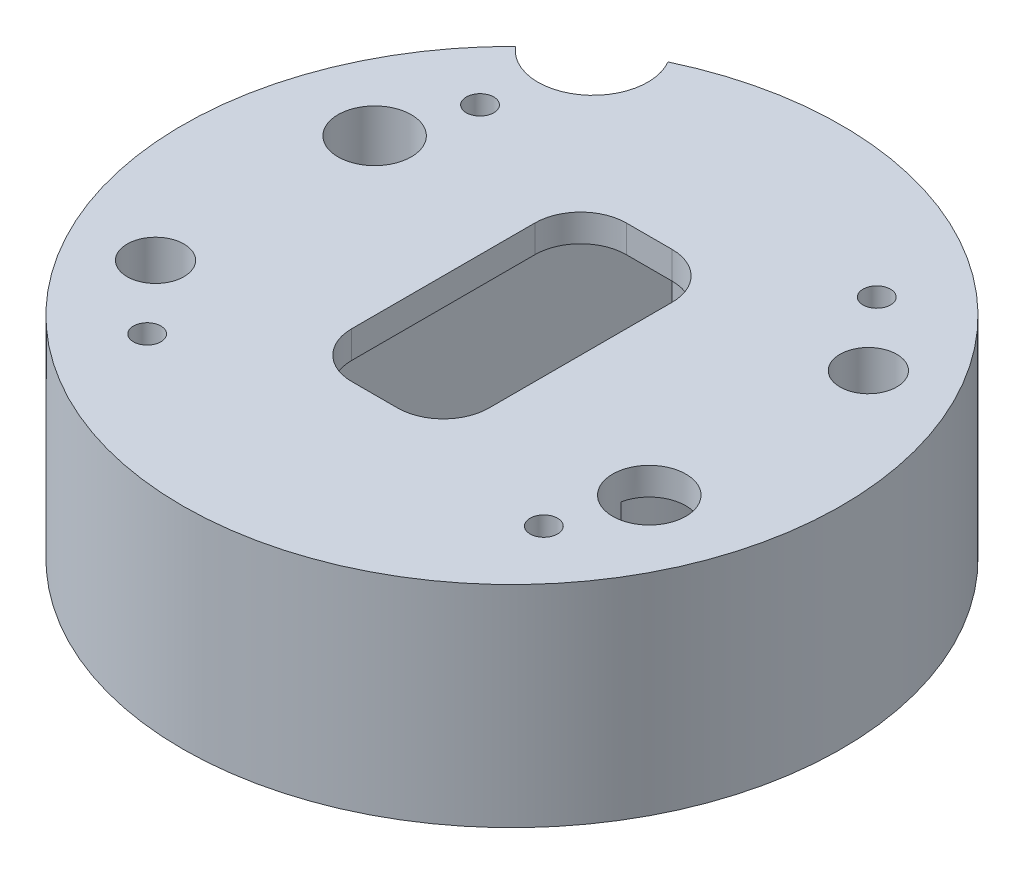
SolidWorks part; units mm, degrees
ref_plane "Front Plane" through (0, 0, 0) normal (0, 0, 1) x (1, 0, 0)
ref_plane "Top Plane" through (0, 0, 0) normal (0, 1, 0) x (1, 0, 0)
ref_plane "Right Plane" through (0, 0, 0) normal (1, 0, 0) x (0, 0, -1)
sketch "Sketch1" plane through (0, 0, 0) normal (0, 1, 0) x (1, 0, 0)
  line L0 (-13, 30.5) -> (13, -30.5) construction
  line L1 (-13, 30.5) -> (13, 30.5)
  line L2 (-13, 30.5) -> (-13, -30.5)
  line L3 (-13, -30.5) -> (13, -30.5)
  line L4 (13, 30.5) -> (13, -30.5)
  line L5 (-24.5, 0) -> (24.5, 0) construction
  line L6 (-34, 0) -> (-36, 0) construction
  line L7 (34, 0) -> (36, 0) construction
  line L8 (-15, 0) -> (-13, 0) construction
  circle A0 centre (0, 0) radius 36
  circle A3 centre (-24.5, 0) radius 9.5
  circle A4 centre (24.5, 0) radius 9.5
  point P5 (0, 0)
  point P12 (0, 0)
  dimension "D1" = 72
  dimension "D2" = 61
  dimension "D4" = 19
  dimension "D3" = 26
extrude "Boss-Extrude1" add sketch "Sketch1" along normal blind 20
sketch "Sketch4" plane through (0, 20, 0) normal (0, 1, 0) x (1, 0, 0)
  line L0 (-24.5, 9.5) -> (-24.5, 0) construction
  line L1 (-24.5, 0) -> (24.5, 0) construction
  line L2 (24.5, 0) -> (24.5, -9.5) construction
  line L3 (-24.5, 9.5) -> (-1.5428, 9.5) construction
  circle A0 centre (-24.5, 9.5) radius 4
  circle A1 centre (-24.5, 0) radius 9.5 construction
  circle A3 centre (24.5, -9.5) radius 4
  circle A5 centre (24.5, 0) radius 9.5 construction
  point P4 (24.5, -9.5)
  dimension "D1" = 8
extrude "Cut-Extrude6" cut sketch "Sketch4" against normal through all
sketch "Sketch5" plane through (0, 20, 0) normal (0, 1, 0) x (1, 0, 0)
  line L0 (0, 0) -> (20.0764, 0) construction
  line L1 (-18.1808, -21.667) -> (21.667, -18.1808) construction
  line L2 (-18.1808, -21.667) -> (-21.667, 18.1808) construction
  line L3 (-21.667, 18.1808) -> (18.1808, 21.667) construction
  line L4 (21.667, -18.1808) -> (18.1808, 21.667) construction
  line L5 (-18.1808, -21.667) -> (18.1808, 21.667) construction
  line L6 (-21.667, 18.1808) -> (21.667, -18.1808) construction
  circle A0 centre (-21.667, 18.1808) radius 1.5
  circle A1 centre (-18.1808, -21.667) radius 1.5
  circle A2 centre (21.667, -18.1808) radius 1.5
  circle A3 centre (18.1808, 21.667) radius 1.5
  circle A4 centre (-21.667, 18.1808) radius 2.3
  circle A5 centre (18.1808, 21.667) radius 2.3
  circle A6 centre (21.667, -18.1808) radius 2.3
  circle A7 centre (-18.1808, -21.667) radius 2.3
  point P0 (0, 0)
  dimension "D2" = 3
  dimension "D3" = 4.6
  dimension "D1" = 40
  dimension "D4" = 85
extrude "Cut-Extrude2" cut sketch "Sketch5" against normal blind 20 contours A0 | A3 | A1 | A2 region at (-21.667, 20, -18.1808) region at (-18.1808, 20, 21.667) region at (21.667, 20, 18.1808) region at (18.1808, 20, -21.667)
sketch "Sketch6" plane through (0, 20, 0) normal (0, 1, 0) x (1, 0, 0)
  line L0 (-24.6817, -14.25) -> (24.6817, 14.25) construction
  line L1 (0, 0) -> (24.909, 0) construction
  circle A0 centre (-24.6817, -14.25) radius 3.1
  circle A1 centre (24.6817, 14.25) radius 3.1
  point P4 (0, 0)
  dimension "D1" = 6.2
  dimension "D2" = 57
  dimension "D3" = 30
extrude "Cut-Extrude4" cut sketch "Sketch6" against normal through all both and the other way through all
sketch "Sketch7" plane through (0, 20, 0) normal (0, 1, 0) x (1, 0, 0)
  line L0 (-20.6488, 29.4895) -> (0, 0) construction
  line L1 (0, 0) -> (0, 21.7628) construction
  arc A0 (-25.2598, 25.6504) -> (-15.4641, 32.5094) centre (-20.6488, 29.4895) ccw
  circle A1 centre (0, 0) radius 36 construction
  arc A2 (-15.4641, 32.5094) -> (-25.2598, 25.6504) centre (0, 0) ccw
  dimension "D1" = 6
  dimension "D2" = 35
extrude "Cut-Extrude5" cut sketch "Sketch7" against normal through all both
sketch "Sketch9" plane through (0, 20, 0) normal (0, 1, 0) x (1, 0, 0)
  line L1 (-7.5, -15) -> (7.5, -15)
  line L2 (-7.5, -15) -> (-7.5, 15)
  line L3 (-7.5, 15) -> (7.5, 15)
  line L4 (-13, -30.5) -> (13, -30.5)
  line L5 (-13, 30.5) -> (-13, -30.5)
  line L6 (13, 30.5) -> (-13, 30.5)
  line L7 (13, -30.5) -> (13, 30.5)
  line L8 (-13, -30.5) -> (13, -30.5)
  line L9 (-13, 30.5) -> (-13, -30.5)
  line L10 (13, 30.5) -> (-13, 30.5)
  line L11 (13, -30.5) -> (13, 30.5)
  line L12 (7.5, -15) -> (7.5, 15)
  line L13 (-7.5, -15) -> (7.5, 15) construction
  line L14 (-7.5, 15) -> (7.5, -15) construction
  arc A0 (-28.4104, 8.6579) -> (-20.5896, 8.6579) centre (-24.5, 9.5) ccw
  circle A1 centre (21.667, -18.1808) radius 1.5
  arc A2 (20.5896, -8.6579) -> (28.4104, -8.6579) centre (24.5, -9.5) ccw
  arc A3 (28.4104, -8.6579) -> (20.5896, -8.6579) centre (24.5, 0) ccw
  arc A4 (20.5896, -8.6579) -> (28.4104, -8.6579) centre (24.5, -9.5) ccw
  arc A5 (28.4104, -8.6579) -> (20.5896, -8.6579) centre (24.5, 0) ccw
  arc A6 (-20.5896, 8.6579) -> (-28.4104, 8.6579) centre (-24.5, 9.5) ccw
  arc A7 (-28.4104, 8.6579) -> (-20.5896, 8.6579) centre (-24.5, 0) ccw
  arc A8 (-20.5896, 8.6579) -> (-28.4104, 8.6579) centre (-24.5, 9.5) ccw
  arc A9 (-28.4104, 8.6579) -> (-20.5896, 8.6579) centre (-24.5, 0) ccw
  circle A10 centre (21.667, -18.1808) radius 1.5
  circle A11 centre (-18.1808, -21.667) radius 1.5
  circle A12 centre (-18.1808, -21.667) radius 1.5
  circle A13 centre (18.1808, 21.667) radius 1.5
  circle A14 centre (18.1808, 21.667) radius 1.5
  circle A15 centre (-21.667, 18.1808) radius 1.5
  circle A16 centre (-21.667, 18.1808) radius 1.5
  circle A17 centre (24.6817, 14.25) radius 3.1
  circle A18 centre (24.6817, 14.25) radius 3.1
  circle A19 centre (-24.6817, -14.25) radius 3.1
  circle A20 centre (-24.6817, -14.25) radius 3.1
  arc A21 (28.4104, -8.6579) -> (20.5896, -8.6579) centre (24.5, -9.5) ccw
  arc A22 (-25.2598, 25.6504) -> (-15.4641, 32.5094) centre (-20.6488, 29.4895) ccw
  arc A23 (-25.2598, 25.6504) -> (-15.4641, 32.5094) centre (0, 0) ccw
  arc A24 (-25.2598, 25.6504) -> (-15.4641, 32.5094) centre (-20.6488, 29.4895) ccw
  arc A25 (-25.2598, 25.6504) -> (-15.4641, 32.5094) centre (0, 0) ccw
  arc M17 (-15.4641, 32.5094) -> (-25.2598, 25.6504) centre (-20.6488, 29.4895) cw
  arc M18 (-25.2598, 25.6504) -> (-15.4641, 32.5094) centre (0, 0) ccw
  circle M19 centre (-24.6817, -14.25) radius 3.1
  circle M20 centre (24.6817, 14.25) radius 3.1
  circle M21 centre (-21.667, 18.1808) radius 1.5
  circle M22 centre (18.1808, 21.667) radius 1.5
  circle M23 centre (-18.1808, -21.667) radius 1.5
  circle M24 centre (21.667, -18.1808) radius 1.5
  arc M25 (-28.4104, 8.6579) -> (-20.5896, 8.6579) centre (-24.5, 9.5) cw
  arc M26 (-20.5896, 8.6579) -> (-28.4104, 8.6579) centre (-24.5, 0) cw
  arc M27 (28.4104, -8.6579) -> (20.5896, -8.6579) centre (24.5, -9.5) cw
  arc M28 (20.5896, -8.6579) -> (28.4104, -8.6579) centre (24.5, 0) cw
  line M29 (13, -30.5) -> (-13, -30.5)
  line M30 (-13, -30.5) -> (-13, 30.5)
  line M31 (-13, 30.5) -> (13, 30.5)
  line M32 (13, 30.5) -> (13, -30.5)
  dimension "D11" = 15
  dimension "D12" = 30
  dimension "D1" = 0
  dimension "D2" = 0
  dimension "D3" = 0
  dimension "D4" = 0
  dimension "D5" = 0
  dimension "D6" = 0
  dimension "D7" = 0
  dimension "D8" = 0
  dimension "D9" = 0
  dimension "D10" = 0
extrude "Boss-Extrude2" add sketch "Sketch9" along normal blind 3 contours M18 M17 M19 M21 M23 M26 M25 M28 M27 M32 M29 M30 M31 M24 M22 M20 | A0 M26 | A21 M28 | M29 M32 M31 M30 region at (-12.3369, 20, 0) region at (-24.5, 20, 0.6723) region at (24.5, 20, -0.6723) region at (-16.6233, 20, -23.7405)
fillet "Fillet1" radius 5 4 edges at (7.5, 21.5, 15) (-7.5, 21.5, 15) (-7.5, 21.5, -15) (7.5, 21.5, -15)
